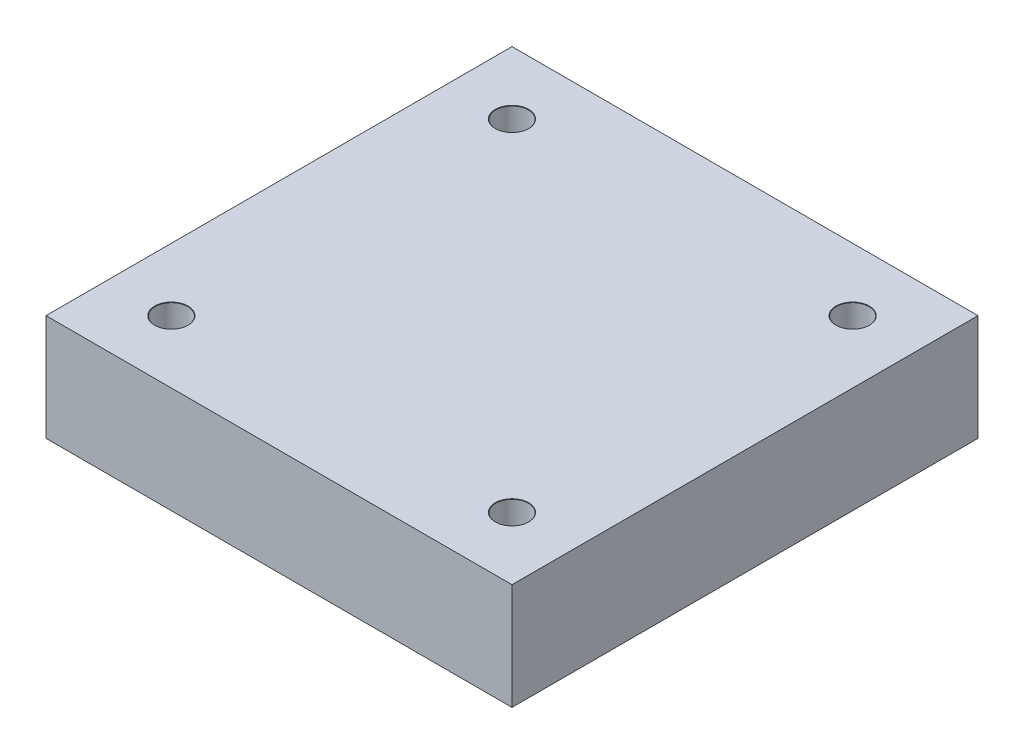
SolidWorks part; units mm, degrees
ref_plane "Front Plane" through (0, 0, 0) normal (0, 0, 1) x (1, 0, 0)
ref_plane "Top Plane" through (0, 0, 0) normal (0, 1, 0) x (1, 0, 0)
ref_plane "Right Plane" through (0, 0, 0) normal (1, 0, 0) x (0, 0, -1)
sketch "Sketch1" plane through (0, 0, 0) normal (0, 1, 0) x (1, 0, 0)
  line L1 (-17.1, 17.1) -> (17.1, 17.1)
  line L2 (-17.1, 17.1) -> (-17.1, -17.1)
  line L3 (-17.1, -17.1) -> (17.1, -17.1)
  line L4 (17.1, 17.1) -> (17.1, -17.1)
  line L5 (-17.1, 17.1) -> (17.1, -17.1) construction
  line L6 (-17.1, -17.1) -> (17.1, 17.1) construction
  point P0 (0, 0)
  dimension "D1" = 34.2
extrude "Boss-Extrude1" add sketch "Sketch1" along normal mid plane 7.8
sketch "Sketch5" plane through (0, 3.9, 0) normal (0, 1, 0) x (1, 0, 0)
  line L1 (12.5, -12.5) -> (-12.5, -12.5) construction
  line L2 (12.5, -12.5) -> (12.5, 12.5) construction
  line L3 (12.5, 12.5) -> (-12.5, 12.5) construction
  line L4 (-12.5, -12.5) -> (-12.5, 12.5) construction
  line L7 (-12.5, -12.5) -> (0, 0) construction
  line L8 (0, 0) -> (-12.5, 12.5) construction
  point P1 (-12.5, 12.5)
  point P2 (12.5, -12.5)
  point P3 (12.5, 12.5)
  point P4 (-12.5, -12.5)
  dimension "D1" = 25
hole_wizard "M2 Clearance Hole1" positions "Sketch5" profile "Sketch8" hole size "M2" standard "ISO" end condition through all
sketch "Sketch8" plane through (-12.5, 3.9, -12.5) normal (1, 0, 0) x (0, 0, 1)
  line L0 (0, 0) -> (0, 7.8)
  line L1 (0, 7.8) -> (1.2, 7.8)
  line L2 (1.2, 7.8) -> (1.2, 0.025)
  line L3 (1.2, 0.025) -> (1.225, 0)
  line L5 (1.225, 0) -> (0, 0)
  line L6 (-1.2, 0.025) -> (-1.225, 0) construction
  line L11 (0, -6.35) -> (0, 107.95) construction
  dimension "Thru Hole Dia." = 2.4
  dimension "Thru Hole Depth" = 7.8
  dimension "Near C'Sink Dia." = 2.45
  dimension "Near C'Sink Angle" = 90
